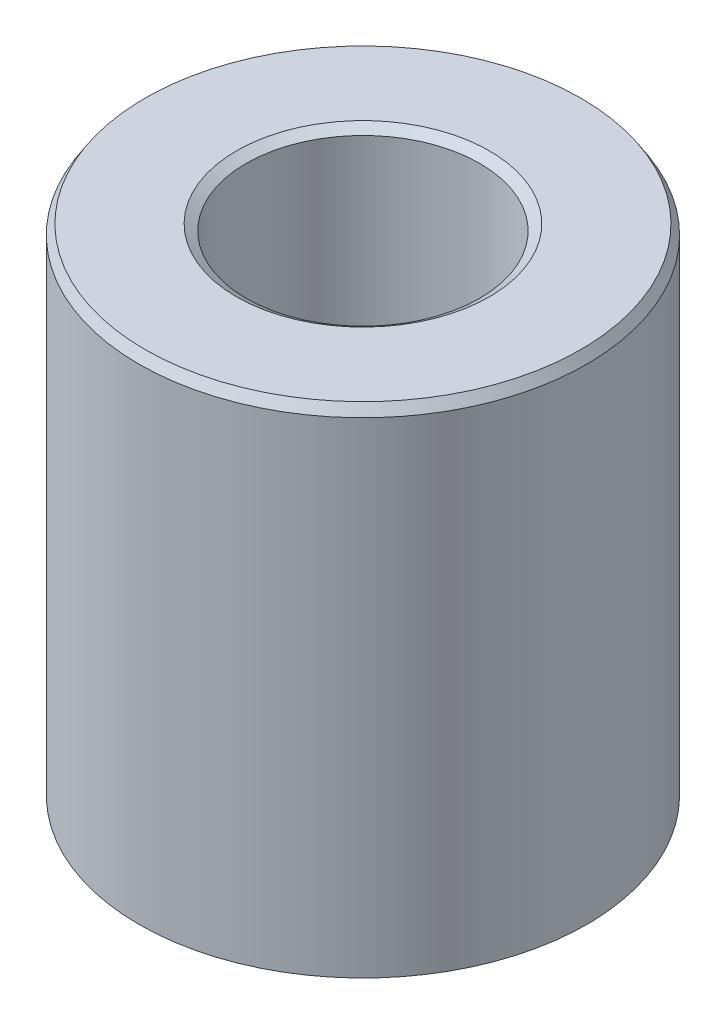
SolidWorks part; units mm, degrees
ref_plane "Front Plane" through (0, 0, 0) normal (0, 0, 1) x (1, 0, 0)
ref_plane "Top Plane" through (0, 0, 0) normal (0, 1, 0) x (1, 0, 0)
ref_plane "Right Plane" through (0, 0, 0) normal (1, 0, 0) x (0, 0, -1)
sketch "Sketch1" plane through (0, 0, 0) normal (0, 1, 0) x (1, 0, 0)
  circle A0 centre (0, 0) radius 50
  dimension "SLEEVE_OD" = 100
extrude "Boss-Extrude1" add sketch "Sketch1" along normal blind 111.8644
sketch "Sketch2" plane through (0, 0, 0) normal (0, 1, 0) x (1, 0, 0)
  circle A0 centre (0, 0) radius 26.0898
  dimension "BORE_D" = 52.1795
extrude "Cut-Extrude1" cut sketch "Sketch2" along normal through all
chamfer "Chamfer1" distance 2.1534 angle 32.188 4 edges at (0, 111.8644, 26.0898) (0, 0, 26.0898) (0, 0, 50) (0, 111.8644, 50) first distance on face at (0, 111.8644, 26.0898) first distance on face at (0, 0, 26.0898) first distance on face at (0, 111.8644, 50)
